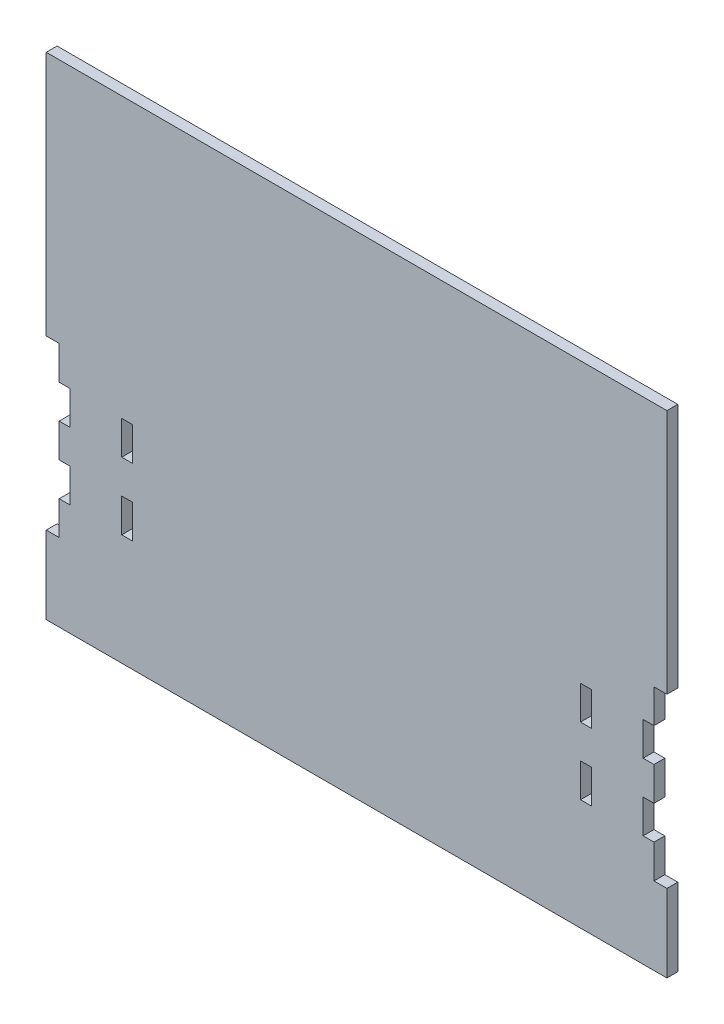
SolidWorks part; units mm, degrees
ref_plane "Front Plane" through (0, 0, 0) normal (0, 0, 1) x (1, 0, 0)
ref_plane "Top Plane" through (0, 0, 0) normal (0, 1, 0) x (1, 0, 0)
ref_plane "Right Plane" through (0, 0, 0) normal (1, 0, 0) x (0, 0, -1)
sketch "Sketch1" plane through (0, 0, 0) normal (0, 0, 1) x (1, 0, 0)
  line L1 (-152.4, 120.65) -> (152.4, 120.65)
  line L2 (-152.4, 120.65) -> (-152.4, -120.65)
  line L3 (-152.4, -120.65) -> (152.4, -120.65)
  line L4 (152.4, 120.65) -> (152.4, -120.65)
  line L5 (-152.4, 120.65) -> (152.4, -120.65) construction
  line L6 (-152.4, -120.65) -> (152.4, 120.65) construction
  point P0 (0, 0)
  dimension "D1" = 241.3
  dimension "D2" = 304.8
extrude "Boss-Extrude1" add sketch "Sketch1" along normal blind 5.334
sketch "Sketch2" plane through (0, 0, 0) normal (0, 0, -1) x (-1, 0, 0)
  line L0 (152.4, 120.65) -> (152.4, -120.65) construction
  line L1 (152.4, 0) -> (146.05, 0)
  line L2 (152.4, 0) -> (152.4, -82.55)
  line L3 (152.4, -82.55) -> (146.05, -82.55)
  line L4 (146.05, 0) -> (146.05, -82.55)
  line L5 (-152.4, -120.65) -> (-152.4, 120.65) construction
  line L6 (-152.4, 0) -> (-146.05, 0)
  line L7 (-152.4, 0) -> (-152.4, -82.55)
  line L8 (-152.4, -82.55) -> (-146.05, -82.55)
  line L9 (-146.05, 0) -> (-146.05, -82.55)
  line L10 (152.4, -120.65) -> (-152.4, -120.65) construction
  dimension "D1" = 82.55
  dimension "D2" = 82.55
  dimension "D3" = 38.1
  dimension "D4" = 38.1
  dimension "D5" = 6.35
  dimension "D6" = 6.35
extrude "Cut-Extrude1" cut sketch "Sketch2" against normal through all
sketch "Sketch9" plane through (0, 0, 5.334) normal (0, 0, 1) x (1, 0, 0)
  line L0 (-146.05, 0) -> (-146.05, -82.55) construction
  line L1 (-146.05, -16.51) -> (-140.716, -16.51)
  line L2 (-146.05, -16.51) -> (-146.05, -33.02)
  line L3 (-146.05, -33.02) -> (-140.716, -33.02)
  line L4 (-140.716, -16.51) -> (-140.716, -33.02)
  line L5 (-146.05, 0) -> (-140.716, 0) construction
  line L6 (-146.05, -49.53) -> (-140.716, -49.53)
  line L7 (-146.05, -49.53) -> (-146.05, -66.04)
  line L8 (-146.05, -66.04) -> (-140.716, -66.04)
  line L9 (-140.716, -49.53) -> (-140.716, -66.04)
  line L10 (-140.716, 0) -> (-140.716, -16.51) construction
  line L11 (-140.716, -33.02) -> (-140.716, -49.53) construction
  line L12 (-146.05, -82.55) -> (-140.716, -82.55) construction
  line L13 (-140.716, -82.55) -> (-140.716, -66.04) construction
  line L14 (0, -120.65) -> (0, 120.65) construction
  line L15 (-152.4, -120.65) -> (152.4, -120.65) construction
  line L16 (152.4, 120.65) -> (-152.4, 120.65) construction
  line L17 (140.716, -82.55) -> (140.716, -66.04) construction
  line L18 (146.05, -82.55) -> (140.716, -82.55) construction
  line L19 (140.716, -33.02) -> (140.716, -49.53) construction
  line L20 (140.716, 0) -> (140.716, -16.51) construction
  line L21 (146.05, 0) -> (140.716, 0) construction
  line L22 (140.716, -49.53) -> (140.716, -66.04)
  line L23 (146.05, -66.04) -> (140.716, -66.04)
  line L24 (146.05, -49.53) -> (146.05, -66.04)
  line L25 (146.05, -49.53) -> (140.716, -49.53)
  line L26 (140.716, -16.51) -> (140.716, -33.02)
  line L27 (146.05, -33.02) -> (140.716, -33.02)
  line L28 (146.05, -16.51) -> (146.05, -33.02)
  line L29 (146.05, -16.51) -> (140.716, -16.51)
  dimension "D1" = 5.334
extrude "Cut-Extrude2" cut sketch "Sketch9" against normal through all
sketch "Sketch23" plane through (0, 0, 5.334) normal (0, 0, 1) x (1, 0, 0)
  line L0 (-140.716, -24.765) -> (-61.976, -24.765) construction
  line L1 (-140.716, -33.02) -> (-140.716, -16.51) construction
  line L2 (-140.716, -16.51) -> (-109.982, -16.51) construction
  line L3 (-140.716, -33.02) -> (-109.982, -33.02) construction
  line L4 (-146.05, -41.275) -> (146.05, -41.275) construction
  line L5 (-146.05, -33.02) -> (-146.05, -49.53) construction
  line L6 (146.05, -49.53) -> (146.05, -33.02) construction
  line L7 (-140.716, -49.53) -> (-109.982, -49.53) construction
  line L8 (-140.716, -57.785) -> (-61.976, -57.785) construction
  line L9 (-140.716, -66.04) -> (-109.982, -66.04) construction
  line L10 (0, -120.65) -> (0, 120.65) construction
  line L11 (-152.4, -120.65) -> (152.4, -120.65) construction
  line L12 (152.4, 120.65) -> (-152.4, 120.65) construction
  line L13 (140.716, -66.04) -> (109.982, -66.04) construction
  line L14 (140.716, -49.53) -> (109.982, -49.53) construction
  line L15 (140.716, -33.02) -> (109.982, -33.02) construction
  line L16 (140.716, -16.51) -> (109.982, -16.51) construction
  line L17 (-109.982, -66.04) -> (-115.316, -66.04)
  line L18 (109.982, -16.51) -> (115.316, -16.51)
  line L19 (109.982, -16.51) -> (109.982, -33.02)
  line L20 (109.982, -33.02) -> (115.316, -33.02)
  line L21 (115.316, -16.51) -> (115.316, -33.02)
  line L22 (109.982, -49.53) -> (115.316, -49.53)
  line L23 (109.982, -49.53) -> (109.982, -66.04)
  line L24 (109.982, -66.04) -> (115.316, -66.04)
  line L25 (115.316, -49.53) -> (115.316, -66.04)
  line L26 (-115.316, -49.53) -> (-115.316, -66.04)
  line L27 (-109.982, -49.53) -> (-109.982, -66.04)
  line L28 (-109.982, -49.53) -> (-115.316, -49.53)
  line L29 (-109.982, -33.02) -> (-115.316, -33.02)
  line L30 (-115.316, -16.51) -> (-115.316, -33.02)
  line L31 (-109.982, -16.51) -> (-115.316, -16.51)
  line L32 (-109.982, -16.51) -> (-109.982, -33.02)
  line L33 (140.716, -16.51) -> (140.716, -33.02) construction
  dimension "D1" = 5.334
  dimension "D2" = 5.334
  dimension "D3" = 25.4
  dimension "D4" = 25.4
extrude "Cut-Extrude8" cut sketch "Sketch23" against normal through all
equation "\"MDF\"= .21in"
equation "\"Foamcore\"= .13in"
equation "\"Gmaterial\"= \"MDF\""
equation "\"D1@Sketch9\"=\"MDF\""
equation "\"D1@Sketch23\"=\"MDF\""
equation "\"D2@Sketch23\"=\"D1@Sketch23\""
equation "\"D1@Boss-Extrude1\"=\"MDF\""
